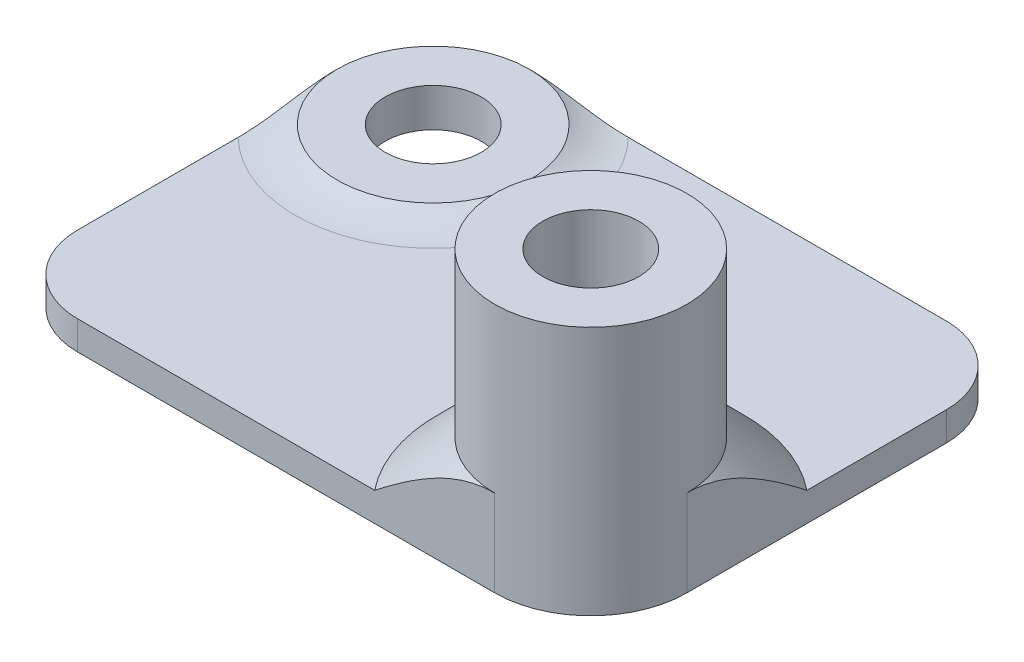
SolidWorks part; units mm, degrees
ref_plane "Front Plane" through (0, 0, 0) normal (0, 0, 1) x (1, 0, 0)
ref_plane "Top Plane" through (0, 0, 0) normal (0, 1, 0) x (1, 0, 0)
ref_plane "Right Plane" through (0, 0, 0) normal (1, 0, 0) x (0, 0, -1)
sketch "Sketch1" plane through (0, 0, 0) normal (0, 1, 0) x (1, 0, 0)
  line L0 (0, 0) -> (-20.7, 12.5) construction
  line L1 (-25.7, 6.25) -> (5, 6.25) construction
  line L2 (-20.7, 17.5) -> (5, 17.5)
  line L3 (-25.7, 12.5) -> (-25.7, -5)
  line L4 (-25.7, -5) -> (0, -5)
  line L5 (5, 17.5) -> (5, 0)
  line L6 (-25.7, 12.5) -> (-25.7, 17.5)
  line L7 (-25.7, 17.5) -> (-20.7, 17.5)
  line L8 (0, -5) -> (5, -5)
  line L9 (5, -5) -> (5, 0)
  circle A0 centre (0, 0) radius 2.5
  circle A1 centre (-20.7, 12.5) radius 2.5
  circle A2 centre (-20.7, 12.5) radius 5
  circle A3 centre (0, 0) radius 5
  arc A4 (-20.7, 17.5) -> (-25.7, 12.5) centre (-20.7, 12.5) ccw construction
  arc A5 (0, -5) -> (5, 0) centre (0, 0) ccw construction
  arc A8 (-25.7, 12.5) -> (-16.4199, 9.9154) centre (-20.7, 12.5) ccw construction
  arc A9 (-16.4199, 9.9154) -> (-20.7, 17.5) centre (-20.7, 12.5) ccw construction
  arc A10 (5, 0) -> (-4.2801, 2.5846) centre (0, 0) ccw construction
  arc A11 (-4.2801, 2.5846) -> (0, -5) centre (0, 0) ccw construction
  point P13 (-10.35, 6.25)
  dimension "D3" = 5
  dimension "D4" = 10
  dimension "D5" = 10
  dimension "D2" = 12.5
  dimension "D1" = 20.7
extrude "Boss-Extrude1" add sketch "Sketch1" against normal blind 1.5 contours L3 L4 A5 L5 L2 A4 A2 A3 | A2 A1 | A3 A0 region at (-10.35, 0, -6.25) region at (-17.2645, 0, -15.9355) region at (3.4355, 0, 3.4355)
extrude "Boss-Extrude2" add sketch "Sketch1<3>" along normal blind 0.5 contours A2 A1 region at (-17.2645, 0, -15.9355)
sketch "Sketch1<3>" plane through (0, 0, 0) normal (0, 1, 0) x (1, 0, 0) same geometry as "Sketch1"
extrude "Boss-Extrude3" add sketch "Sketch1<4>" along normal blind 11.5 contours A3 A0 region at (3.4355, 0, 3.4355)
sketch "Sketch1<4>" plane through (0, 0, 0) normal (0, 1, 0) x (1, 0, 0) same geometry as "Sketch1"
fillet "Fillet1" radius 5 1 edges at (-17.1645, 0, -8.9645)
chamfer "Chamfer1" distance 3 distance2 3 1 edges at (-3.5355, 0, -3.5355)
fillet "Fillet2" radius 4 2 edges at (-25.7, -0.75, 5) (5, -0.75, -17.5)
